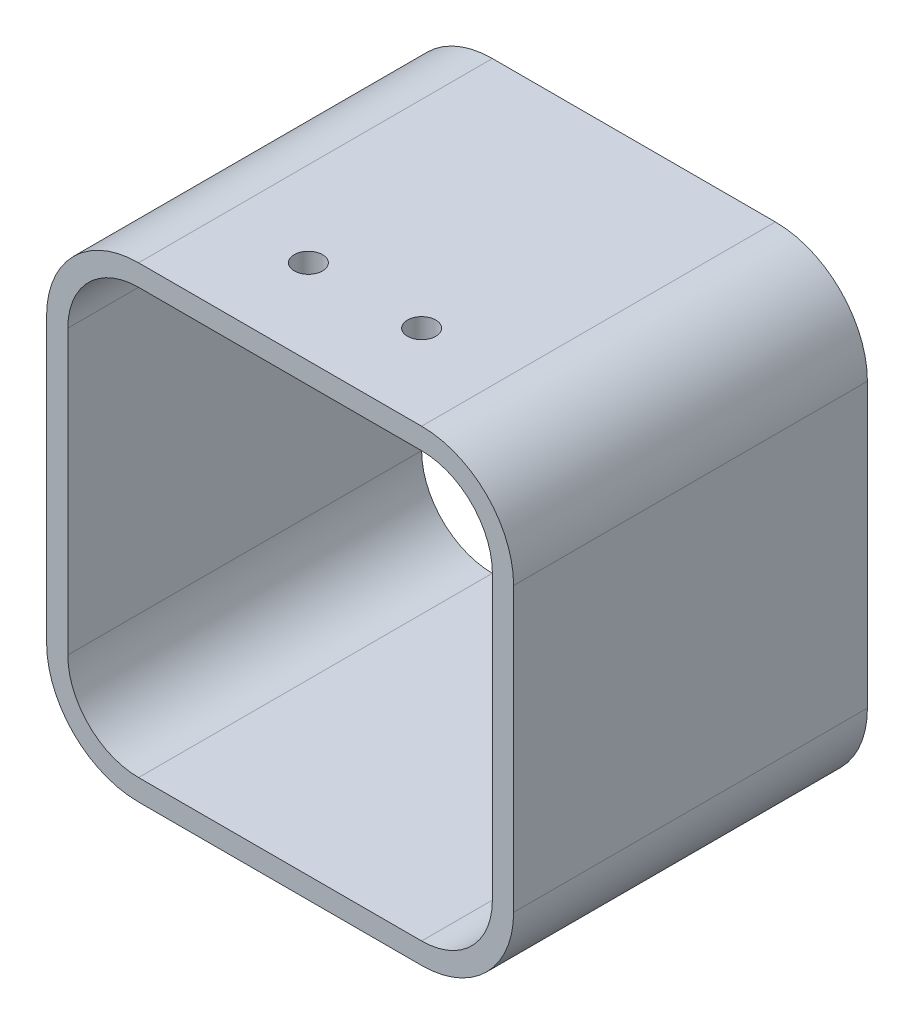
SolidWorks part; units mm, degrees
ref_plane "Piano frontale" through (0, 0, 0) normal (0, 0, 1) x (1, 0, 0)
ref_plane "Piano superiore" through (0, 0, 0) normal (0, 1, 0) x (1, 0, 0)
ref_plane "Piano destro" through (0, 0, 0) normal (1, 0, 0) x (0, 0, -1)
sketch "Schizzo1" plane through (0, 0, 0) normal (0, 0, 1) x (1, 0, 0)
  line L0 (-10, 0) -> (-50, 0)
  line L1 (0, -10) -> (0, -50)
  line L2 (-60, -10) -> (-60, -50)
  line L3 (-50, -60) -> (-10, -60)
  arc A0 (0, -50) -> (-10, -60) centre (-10, -50) cw
  arc A1 (-50, -60) -> (-60, -50) centre (-50, -50) cw
  arc A2 (0, -10) -> (-10, 0) centre (-10, -10) ccw
  arc A3 (-60, -10) -> (-50, 0) centre (-50, -10) cw
  point P7 (0, -60)
  point P10 (-60, -60)
  point P13 (0, 0)
  point P16 (-60, 0)
  dimension "D4" = 10
  dimension "D1" = 60
  dimension "D2" = 60
  dimension "D3" = 60
extrude "Estrusione-Sottile1" add sketch "Schizzo1" along normal blind 50 thin thin type one direction wall 3
sketch "Schizzo2" plane through (0, 3, 0) normal (0, 1, 0) x (1, 0, 0)
  line L0 (-30, 0) -> (-30, -50) construction
  line L1 (-10, 0) -> (-50, 0) construction
  line L2 (-10, -50) -> (-50, -50) construction
  circle A0 centre (-38, -38) radius 2
  circle A1 centre (-22, -38) radius 2
  dimension "D5" = 4
  dimension "D6" = 4
  dimension "D1" = 8
  dimension "D2" = 8
  dimension "D3" = 12
  dimension "D4" = 12
extrude "Taglio-Estrusione1" cut sketch "Schizzo2" against normal blind 10
